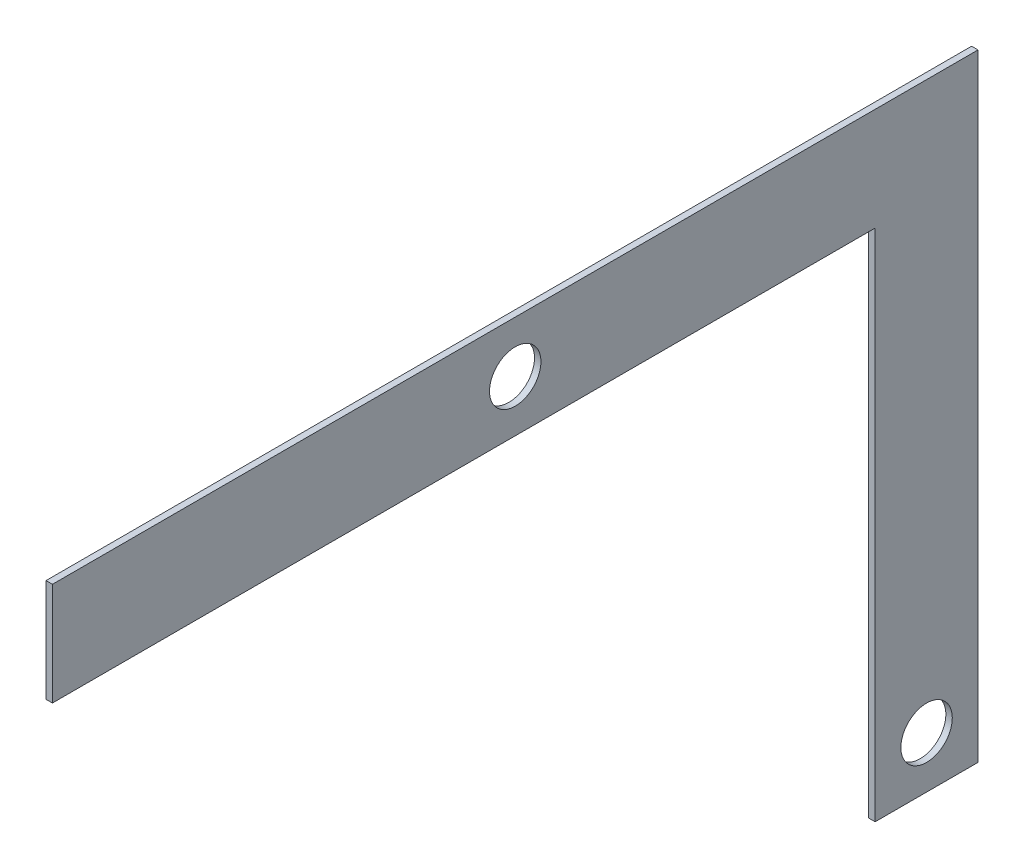
SolidWorks part; units mm, degrees
material "6063-O"
ref_plane "Front" through (0, 0, 0) normal (0, 0, 1) x (1, 0, 0)
ref_plane "Top" through (0, 0, 0) normal (0, 1, 0) x (1, 0, 0)
ref_plane "Right" through (0, 0, 0) normal (1, 0, 0) x (0, 0, -1)
sketch "Sketch1" plane through (0, 0, 0) normal (1, 0, 0) x (0, 0, -1)
  line L0 (0, 25.4) -> (0, -25.4) construction
  line L1 (-228.6, 25.4) -> (228.6, 25.4)
  line L2 (-228.6, 25.4) -> (-228.6, -279.4)
  line L3 (-177.8, -25.4) -> (177.8, -25.4)
  line L4 (228.6, 25.4) -> (228.6, -279.4)
  line L7 (228.6, -279.4) -> (177.8, -279.4)
  line L8 (177.8, -25.4) -> (177.8, -279.4)
  line L11 (-228.6, -279.4) -> (-177.8, -279.4)
  line L12 (-177.8, -25.4) -> (-177.8, -279.4)
  circle A0 centre (0, 0) radius 12.7
  point P12 (0, 0)
  dimension "D5" = 25.4
  dimension "D1" = 50.8
  dimension "D2" = 50.8
  dimension "D3" = 457.2
  dimension "D4" = 254
extrude "Boss-Extrude1" add sketch "Sketch1" along normal blind 3.175
sketch "Sketch3" plane through (3.175, 0, 0) normal (1, 0, 0) x (0, 0, -1)
  line L0 (-279.2989, -254) -> (49720.7011, -254) construction
  line L1 (-228.6, -279.4) -> (-177.8, -279.4) construction
  line L2 (-203.2, -279.4) -> (-203.2, 25.4) construction
  line L3 (228.6, 25.4) -> (-228.6, 25.4) construction
  line L4 (203.2, -279.4) -> (203.2, 25.4) construction
  line L5 (177.8, -279.4) -> (228.6, -279.4) construction
  circle A0 centre (-203.2, -254) radius 12.7
  circle A1 centre (203.2, -254) radius 12.7
  point P12 (-203.2, -254)
  point P13 (203.2, -254)
  dimension "D2" = 25.4
  dimension "D1" = 25.4
extrude "Cut-Extrude1" cut sketch "Sketch3" against normal through all
sketch "Sketch4" plane through (3.175, 0, 0) normal (1, 0, 0) x (0, 0, -1)
  line L1 (-177.8, -25.4) -> (-228.6, -25.4)
  line L2 (-177.8, -25.4) -> (-177.8, -279.4)
  line L3 (-177.8, -279.4) -> (-228.6, -279.4)
  line L4 (-228.6, -25.4) -> (-228.6, -279.4)
extrude "Cut-Extrude2" cut sketch "Sketch4" against normal through all
